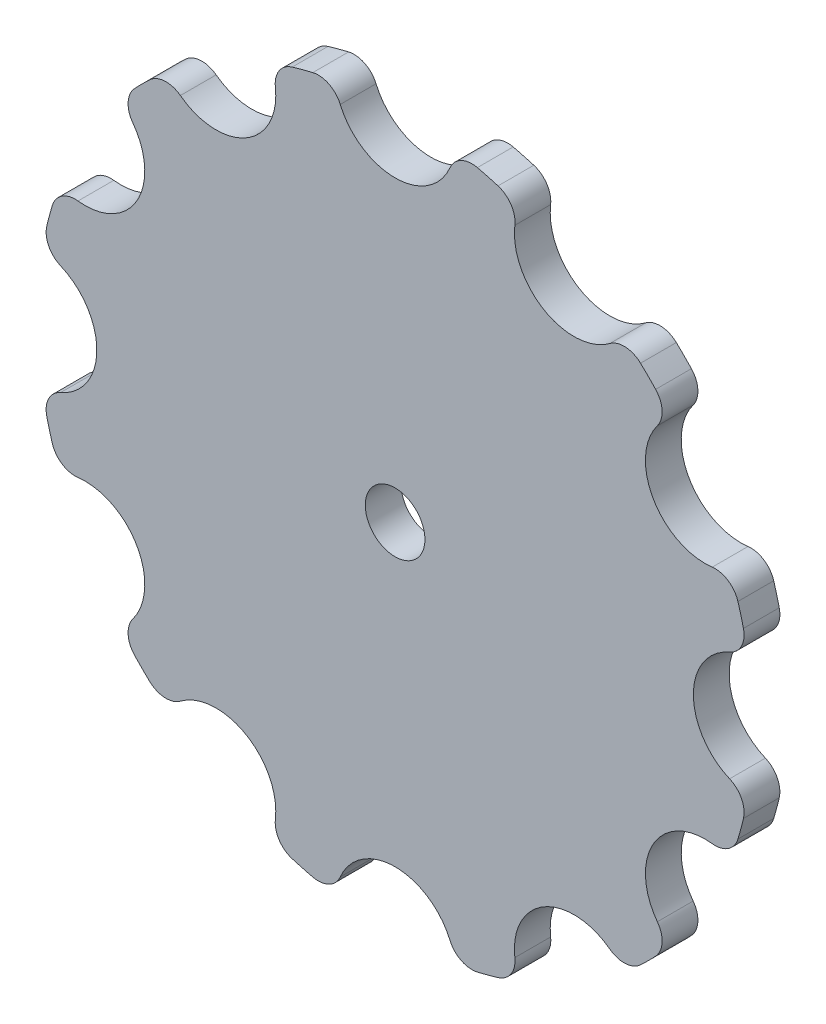
SolidWorks part; units mm, degrees
ref_plane "Front Plane" through (0, 0, 0) normal (0, 0, 1) x (1, 0, 0)
ref_plane "Top Plane" through (0, 0, 0) normal (0, 1, 0) x (1, 0, 0)
ref_plane "Right Plane" through (0, 0, 0) normal (1, 0, 0) x (0, 0, -1)
sketch "Sketch1" plane through (0, 0, 0) normal (0, 0, 1) x (1, 0, 0)
  line L0 (0, 25) -> (0, 30) construction
  circle A0 centre (0, 0) radius 30
  circle A1 centre (0, 0) radius 25 construction
  circle A2 centre (0, 30) radius 5
  circle A3 centre (15, 25.9808) radius 5
  circle A4 centre (25.9808, 15) radius 5
  circle A5 centre (30, 0) radius 5
  circle A6 centre (25.9808, -15) radius 5
  circle A7 centre (15, -25.9808) radius 5
  circle A8 centre (0, -30) radius 5
  circle A9 centre (-15, -25.9808) radius 5
  circle A10 centre (-25.9808, -15) radius 5
  circle A11 centre (-30, 0) radius 5
  circle A12 centre (-25.9808, 15) radius 5
  circle A13 centre (-15, 25.9808) radius 5
  point P31 (0, 0)
  dimension "D1" = 60
  dimension "D2" = 50
  dimension "D3" = 12
extrude "Boss-Extrude1" add sketch "Sketch1" along normal blind 3 contours A13 A0 A12 A11 A10 A9 A8 A7 A6 A5 A4 A3 A2 region at (0, 0, 0)
fillet "Fillet1" radius 2 4 edges at (-23.1286, 19.1067, 1.5) (-19.1067, 23.1286, 1.5) (-4.9826, 29.5833, 1.5) (-10.4766, 28.1112, 1.5)
fillet "Fillet2" radius 2 20 edges at (-28.1112, 10.4766, 1.5) (-29.5833, 4.9826, 1.5) (-29.5833, -4.9826, 1.5) (-28.1112, -10.4766, 1.5) (-23.1286, -19.1067, 1.5) (-19.1067, -23.1286, 1.5) (-10.4766, -28.1112, 1.5) (-4.9826, -29.5833, 1.5) (4.9826, -29.5833, 1.5) (10.4766, -28.1112, 1.5) (19.1067, -23.1286, 1.5) (23.1286, -19.1067, 1.5) (28.1112, -10.4766, 1.5) (29.5833, -4.9826, 1.5) (29.5833, 4.9826, 1.5) (28.1112, 10.4766, 1.5) (23.1286, 19.1067, 1.5) (19.1067, 23.1286, 1.5) (4.9826, 29.5833, 1.5) (10.4766, 28.1112, 1.5)
sketch "Sketch2" plane through (0, 0, 0) normal (0, 0, -1) x (-1, 0, 0)
  circle A0 centre (0, 0) radius 2.5
  dimension "D1" = 5
extrude "Cut-Extrude1" cut sketch "Sketch2" against normal blind 10
